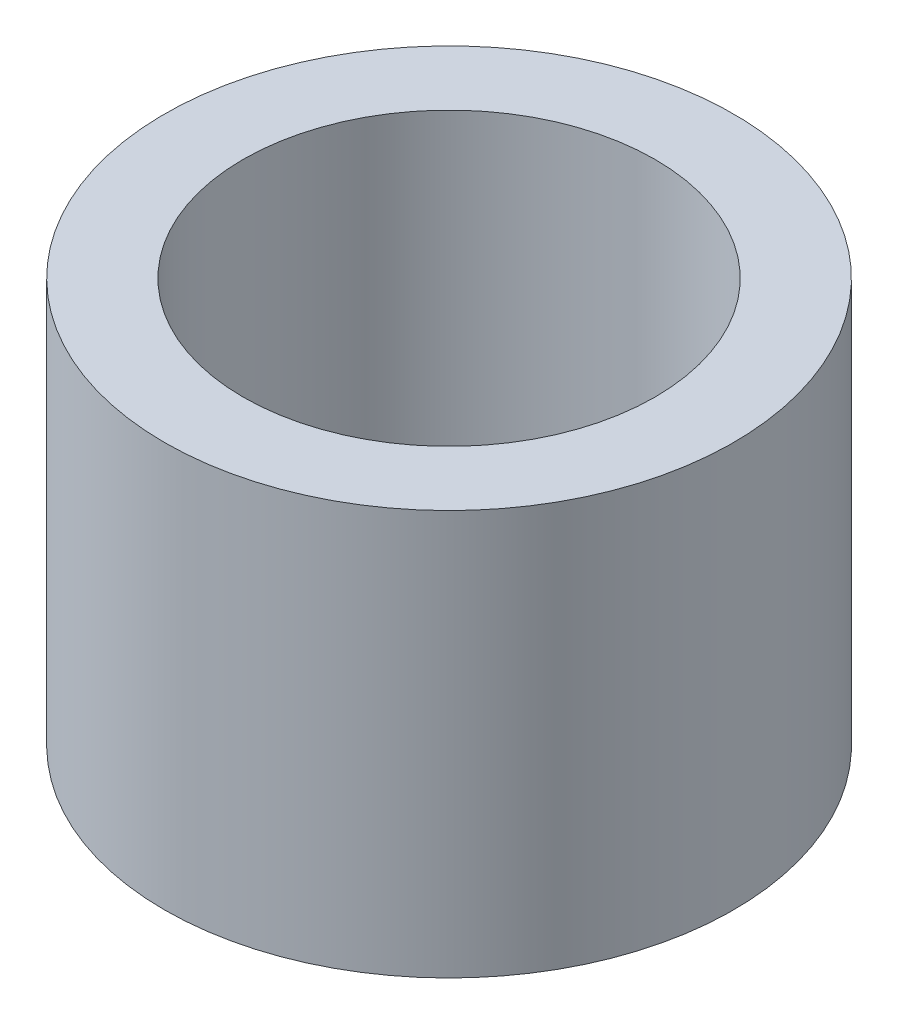
SolidWorks part; units mm, degrees
ref_plane "Front Plane" through (0, 0, 0) normal (0, 0, 1) x (1, 0, 0)
ref_plane "Top Plane" through (0, 0, 0) normal (0, 1, 0) x (1, 0, 0)
ref_plane "Right Plane" through (0, 0, 0) normal (1, 0, 0) x (0, 0, -1)
sketch "Sketch1" plane through (0, 0, 0) normal (0, 1, 0) x (1, 0, 0)
  circle A0 centre (0, 0) radius 22.5
  dimension "SLEEVE_OD" = 45
extrude "Boss-Extrude1" add sketch "Sketch1" along normal blind 32.0111
sketch "Sketch2" plane through (0, 0, 0) normal (0, 1, 0) x (1, 0, 0)
  circle A0 centre (0, 0) radius 16.283
  dimension "BORE_D" = 32.566
extrude "Cut-Extrude1" cut sketch "Sketch2" along normal through all
chamfer "Chamfer1" distance 2.7575 angle 56.554 rebuild error yes
